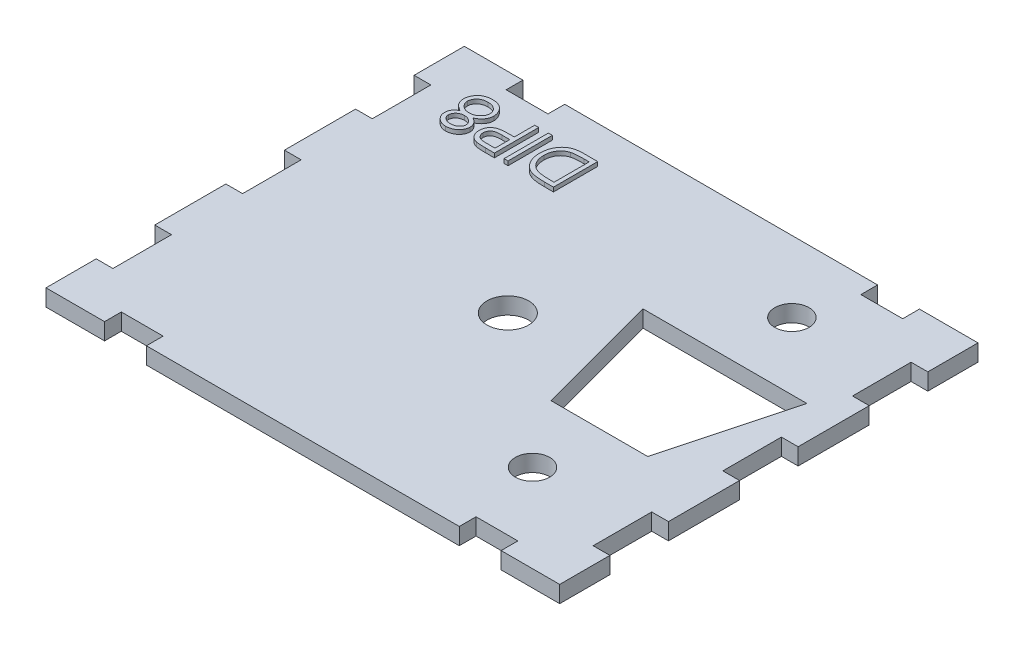
SolidWorks part; units mm, degrees
ref_plane "Front Plane" through (0, 0, 0) normal (0, 0, 1) x (1, 0, 0)
ref_plane "Top Plane" through (0, 0, 0) normal (0, 1, 0) x (1, 0, 0)
ref_plane "Right Plane" through (0, 0, 0) normal (1, 0, 0) x (0, 0, -1)
sketch "Sketch2" plane through (0, 0, 0) normal (0, 1, 0) x (1, 0, 0)
  line L1 (-50, 25) -> (50, 25)
  line L2 (-50, 25) -> (-50, -25)
  line L3 (-50, -25) -> (50, -25)
  line L4 (50, 25) -> (50, -25)
  line L5 (-50, 25) -> (50, -25) construction
  line L6 (-50, -25) -> (50, 25) construction
  point P0 (0, 0)
  dimension "D1" = 100
  dimension "D2" = 50
extrude "Boss-Extrude1" add sketch "Sketch2" along normal blind 2
sketch "Sketch12" plane through (0, 2, 0) normal (0, 1, 0) x (1, 0, 0)
  line L0 (-50, -25) -> (50, -25) construction
  line L1 (-40.2, -25) -> (-50, -25)
  line L2 (-40.2, -25) -> (-40.2, 25)
  line L3 (-40.2, 25) -> (-50, 25)
  line L4 (-50, -25) -> (-50, 25)
  line L5 (-50, -25) -> (50, -25) construction
  line L6 (41.2, -25) -> (50, -25)
  line L7 (41.2, -25) -> (41.2, 25)
  line L8 (41.2, 25) -> (50, 25)
  line L9 (50, -25) -> (50, 25)
extrude "Cut-Extrude8" cut sketch "Sketch12" against normal blind 6
sketch "Sketch13" plane through (0, 2, 0) normal (0, 1, 0) x (1, 0, 0)
  line L1 (-28.2, 19) -> (-30.2, 19)
  line L2 (-28.2, 19) -> (-28.2, 12)
  line L3 (-28.2, 12) -> (-30.2, 12)
  line L4 (-30.2, 19) -> (-30.2, 12)
  line L5 (-28.2, 3.5) -> (-30.2, 3.5)
  line L6 (-28.2, 3.5) -> (-28.2, -3.5)
  line L7 (-28.2, -3.5) -> (-30.2, -3.5)
  line L8 (-30.2, 3.5) -> (-30.2, -3.5)
  line L9 (-28.2, -12) -> (-30.2, -12)
  line L10 (-28.2, -12) -> (-28.2, -19)
  line L11 (-28.2, -19) -> (-30.2, -19)
  line L12 (-30.2, -12) -> (-30.2, -19)
  line L13 (29.2, 19) -> (31.2, 19)
  line L14 (29.2, 19) -> (29.2, 12)
  line L15 (29.2, 12) -> (31.2, 12)
  line L16 (31.2, 19) -> (31.2, 12)
  line L17 (29.2, 3.5) -> (31.2, 3.5)
  line L18 (29.2, 3.5) -> (29.2, -3.5)
  line L19 (29.2, -3.5) -> (31.2, -3.5)
  line L20 (31.2, 3.5) -> (31.2, -3.5)
  line L21 (29.2, -12) -> (31.2, -12)
  line L22 (29.2, -12) -> (29.2, -19)
  line L23 (29.2, -19) -> (31.2, -19)
  line L24 (31.2, -12) -> (31.2, -19)
  line L25 (-40.2, -25) -> (41.2, -25) construction
  line L26 (-23.2, 25) -> (-18.2, 25)
  line L27 (41.2, 25) -> (-40.2, 25) construction
  line L28 (-40.2, -25) -> (41.2, -25) construction
  line L29 (41.2, 25) -> (-40.2, 25) construction
  line L30 (-40.2, -25) -> (41.2, -25) construction
  line L31 (41.2, 25) -> (31.2, 25)
  line L32 (41.2, 25) -> (41.2, -25)
  line L33 (41.2, -25) -> (31.2, -25)
  line L34 (31.2, 25) -> (31.2, -25)
  line L35 (41.2, 25) -> (-40.2, 25) construction
  line L36 (-40.2, -25) -> (-30.2, -25)
  line L37 (-40.2, -25) -> (-40.2, 25)
  line L38 (-40.2, 25) -> (-30.2, 25)
  line L39 (-30.2, -25) -> (-30.2, 25)
  line L40 (-23.2, 25) -> (-23.2, 23)
  line L41 (-23.2, 23) -> (-18.2, 23)
  line L42 (-18.2, 25) -> (-18.2, 23)
  line L43 (-23.2, -25) -> (-18.2, -25)
  line L44 (-23.2, -25) -> (-23.2, -23)
  line L45 (-23.2, -23) -> (-18.2, -23)
  line L46 (-18.2, -25) -> (-18.2, -23)
  line L47 (24.2, -25) -> (19.2, -25)
  line L48 (24.2, -25) -> (24.2, -23)
  line L49 (24.2, -23) -> (19.2, -23)
  line L50 (19.2, -25) -> (19.2, -23)
  line L51 (24.2, 25) -> (19.2, 25)
  line L52 (24.2, 25) -> (24.2, 23)
  line L53 (24.2, 23) -> (19.2, 23)
  line L54 (19.2, 25) -> (19.2, 23)
  point P24 (29.2, 0)
  point P30 (30.2, 3.5)
  line M32 (41.2, -25) -> (41.2, 25)
  line M41 (41.2, 25) -> (-40.2, 25)
  line M42 (-40.2, 25) -> (-40.2, -25)
  line M47 (-40.2, -25) -> (41.2, -25)
  dimension "D1" = 2
  dimension "D2" = 2
  dimension "D3" = 2
  dimension "D4" = 2
  dimension "D5" = 2
  dimension "D6" = 2
  dimension "D7" = 57.4
  dimension "D8" = 57.4
  dimension "D9" = 57.4
  dimension "D10" = 7
  dimension "D11" = 7
  dimension "D12" = 7
  dimension "D13" = 7
  dimension "D14" = 7
  dimension "D15" = 7
  dimension "D16" = 5
  dimension "D17" = 2
  dimension "D18" = 5
  dimension "D19" = 6
  dimension "D20" = 8.5
  dimension "D21" = 8.5
  dimension "D22" = 6
  dimension "D23" = 6
  dimension "D24" = 8.5
  dimension "D25" = 8.5
  dimension "D26" = 6
  dimension "D27" = 5
  dimension "D28" = 5
  dimension "D29" = 2
  dimension "D30" = 2
  dimension "D31" = 5
  dimension "D32" = 5
  dimension "D33" = 5
  dimension "D34" = 5
  dimension "D35" = 2
extrude "Cut-Extrude10" cut sketch "Sketch13" against normal blind 6 contours L5 L8 L7 L6 | L39 L12 L8 L4 M47 M41 M42 | L1 L4 L3 L2 | L50 L48 L49 M47 | L24 L21 L22 L23 | L20 L17 L18 L19 | L16 L13 L14 L15 | L54 L53 L52 M41 | L9 L12 L11 L10 | L34 L16 L20 L24 M41 M47 M32 | L26 L42 L41 L40 | L45 L46 L43 L44 region at (-29.2, 2, -15.5) region at (-35.2, 2, 0) region at (-29.2, 2, 0) region at (-29.2, 2, 15.5) region at (21.7, 2, -24) region at (36.2, 2, 0) region at (21.7, 2, 24) region at (30.2, 2, -15.5) region at (30.2, 2, 0) region at (30.2, 2, 15.5)
sketch "Sketch15" plane through (0, 0, 0) normal (0, -1, 0) x (1, 0, 0)
  line L0 (24.2, 23) -> (19.2, 23) construction
  line L16 (20.7242, -7.5) -> (20.7242, -8.5)
  line L17 (20.7242, -7.5) -> (25.936, -7.5)
  line L18 (25.936, -7.5) -> (22.4527, 5.5)
  line L19 (22.4527, 5.5) -> (12.4527, 5.5)
  line L20 (12.4527, 5.5) -> (8.9693, -7.5)
  line L21 (8.9693, -7.5) -> (14.1811, -7.5)
  line L22 (14.1811, -7.5) -> (14.1811, -8.5)
  line L23 (14.1811, -8.5) -> (7.6661, -8.5)
  line L24 (7.6661, -8.5) -> (11.6853, 6.5)
  line L25 (11.6853, 6.5) -> (23.22, 6.5)
  line L26 (23.22, 6.5) -> (27.2392, -8.5)
  line L27 (27.2392, -8.5) -> (20.7242, -8.5)
  line L28 (20.7242, -8.5) -> (14.1811, -8.5)
  line L29 (14.1811, -7.5) -> (20.7242, -7.5)
  line L31 (29.2, 12) -> (29.2, 19) construction
  dimension "D4" = 16.5
  dimension "D18" = 11.5347
  dimension "D19" = 15.5291
  dimension "D20" = 15.5291
  dimension "D21" = 13.4586
  dimension "D22" = 13.4586
  dimension "D23" = 10
  dimension "D24" = 5.2118
  dimension "D25" = 5.2118
  dimension "D26" = 6.515
  dimension "D27" = 6.515
  dimension "D28" = 1
  dimension "D29" = 105
  dimension "D30" = 105
  dimension "D31" = 75
  dimension "D32" = 75
  dimension "D33" = 5.98
  dimension "D34" = 1
extrude "Cut-Extrude13" cut sketch "Sketch15" against normal blind 10 contours L21 L29 L17 L18 L19 L20 | L27 L26 L25 L24 L23 L22 L21 L20 L19 L18 L17 L16 | L29 L22 L28 L16 region at (23.3301, 0, -7.7466) region at (17.4527, 0, -1.5597) region at (17.4527, 0, -8)
sketch "Sketch16" plane through (0, 0, 0) normal (0, -1, 0) x (-1, 0, 0)
  circle A0 centre (0, 0) radius 2.5
  dimension "D1" = 5
extrude "Cut-Extrude14" cut sketch "Sketch16" against normal blind 10 contours A0
sketch "Sketch17" plane through (0, 0, 0) normal (0, -1, 0) x (-1, 0, 0)
  line L2 (-27.2392, 8.5) -> (-7.6661, 8.5) construction
  line L4 (-11.6853, -6.5) -> (-23.22, -6.5) construction
  circle A0 centre (-17.4527, -14.5) radius 2.05
  circle A1 centre (-17.4527, 16.5) radius 2.05
  dimension "D1" = 4.1
  dimension "D2" = 4.1
  dimension "D3" = 8
  dimension "D4" = 9.7866
  dimension "D5" = 9.7866
  dimension "D6" = 5.7673
  dimension "D7" = 5.7673
  dimension "D8" = 8
extrude "Cut-Extrude15" cut sketch "Sketch17" against normal blind 3.5
sketch "Sketch22" plane through (0, 2, 0) normal (0, 1, 0) x (1, 0, 0)
  line L0 (-24.5837, 20.5398) -> (4.8961, 20.5398) construction
  text T0 "DIP8" font "Century Gothic" height in points 20
extrude "Boss-Extrude4" add sketch "Sketch22" along normal blind 0.5
